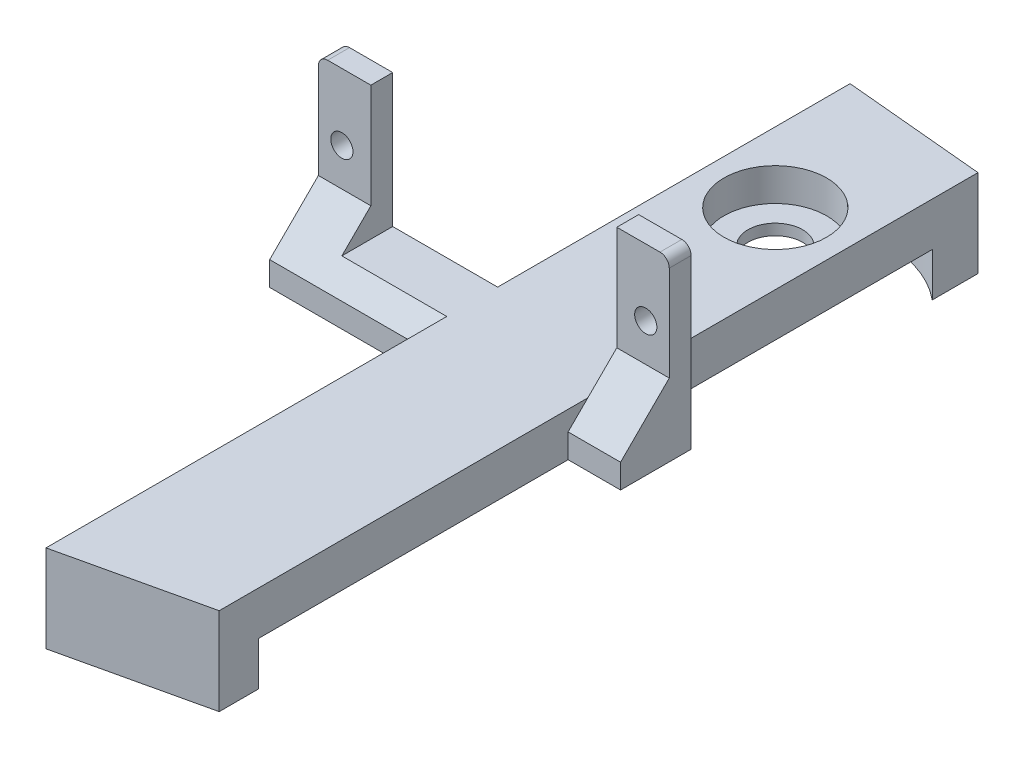
SolidWorks part; units mm, degrees
note: The reader was unsure of these and kept them because the rebuilt part matched: shared geometry of "Sketch2<3>".
ref_plane "Front Plane" through (0, 0, 0) normal (0, 0, 1) x (1, 0, 0)
ref_plane "Top Plane" through (0, 0, 0) normal (0, 1, 0) x (1, 0, 0)
ref_plane "Right Plane" through (0, 0, 0) normal (1, 0, 0) x (0, 0, -1)
sketch "Sketch1" plane through (0, 0, 0) normal (0, 0, 1) x (1, 0, 0)
  line L0 (11.25, -6.1) -> (15.2, -6.1)
  line L1 (11.25, -6.1) -> (11.25, 6.0941)
  line L2 (11.25, 6.0941) -> (15.2, 6.1)
  line L3 (15.2, -6.1) -> (-15.2, -6.1) construction
  line L4 (-10.5, 6.1) -> (-15.2, 6.1) construction
  line L5 (-16.05, 5.25) -> (-16.05, -5.25) construction
  line L6 (-16.05, -5.25) -> (-16.05, -0.55) construction
  line L9 (15.2, -6.1) -> (11.25, -6.1)
  line L10 (-11.25, 6.1) -> (-15.2, 6.1)
  line L11 (-16.05, 5.25) -> (-16.05, -5.25)
  line L12 (-16.05, -5.25) -> (-16.05, -0.55)
  line L13 (16.05, 5.25) -> (16.05, -5.25)
  line L14 (-15.2, -6.1) -> (-16.05, -6.1)
  line L15 (-11.25, 6.1) -> (-11.25, -6.1)
  line L16 (-11.25, -5.25) -> (-11.25, 5.25) construction
  line L17 (-11.25, -5.25) -> (-11.25, 5.25) construction
  line L18 (-15.2, 6.1) -> (15.2, 6.1) construction
  line L19 (-11.25, -6.1) -> (-15.2, -6.1)
  line L20 (-16.05, -5.25) -> (-16.05, -6.1)
  line L21 (15.2, -6.1) -> (16.05, -6.1)
  line L22 (16.05, -5.25) -> (16.05, -6.1)
  arc A0 (-15.2, 6.1) -> (-16.05, 5.25) centre (-15.2, 5.25) ccw construction
  arc A1 (-16.05, -5.25) -> (-15.2, -6.1) centre (-15.2, -5.25) ccw construction
  arc A2 (15.2, -6.1) -> (16.05, -5.25) centre (15.2, -5.25) ccw construction
  arc A3 (16.05, 5.25) -> (15.2, 6.1) centre (15.2, 5.25) ccw construction
  arc A4 (-15.2, 6.1) -> (-16.05, 5.25) centre (-15.2, 5.25) ccw
  arc A5 (-16.05, -5.25) -> (-15.2, -6.1) centre (-15.2, -5.25) ccw
  arc A6 (15.2, -6.1) -> (16.05, -5.25) centre (15.2, -5.25) ccw
  arc A7 (16.05, 5.25) -> (15.2, 6.1) centre (15.2, 5.25) ccw
  circle A8 centre (-13.9, 0) radius 1.016
  circle A9 centre (13.9, 0) radius 1.016
  dimension "D1" = 2.032
  dimension "D2" = 2.032
extrude "Boss-Extrude1" add sketch "Sketch1" along normal blind 2 contours L11 A5 L19 L15 L10 A4 A8 | L13 A7 L2 L1 L0 A6 A9 | A6 L21 L22 | A5 L20 L14
sketch "Sketch2" plane through (0, -6.1, 0) normal (0, -1, 0) x (1, 0, 0)
  line L0 (-16.05, 2) -> (16.05, 2)
  line L5 (16.05, 2) -> (16.05, 0)
  line L6 (16.05, 0) -> (-16.05, 0)
  line L7 (-16.05, 0) -> (-16.05, 2)
  line L8 (-1.65, 41.3173) -> (-1.65, -32.2403)
  line L9 (11.25, 2) -> (11.25, 38.373)
  line L10 (-1.65, -32.2403) -> (11.25, -31.0433)
  line L12 (-27.6754, 45.6063) -> (7.1754, 36.8937) construction
  line L17 (4.75, -29) -> (0.35, -29) construction
  line L18 (-1.65, 39.1) -> (7.1754, 36.8937)
  line L19 (11.25, 0) -> (11.25, -31.0433)
  line L24 (4.75, -29) -> (0.35, -29)
  line L26 (4.75, -29.2) -> (0.35, -29.2)
  line L27 (-1.65, 38.8938) -> (7.1268, 36.6996)
  line L28 (11.12, 34.6396) -> (11.25, 34.5185)
  line L29 (-1.5749, 22.2572) -> (-1.65, 22.613)
  line L30 (-1.65, 41.3173) -> (11.25, 38.373)
  line L32 (-1.6985, 38.906) -> (7.1268, 36.6996) construction
  circle A1 centre (4.75, -19) radius 4.7
  arc A2 (14.75, 27.1922) -> (7.1754, 36.8937) centre (4.75, 27.1922) ccw construction
  arc A3 (4.75, -29) -> (14.75, -19) centre (4.75, -19) ccw construction
  arc A4 (-9.725, -26.277) -> (0.35, -29) centre (0.35, -9) ccw construction
  arc A5 (11.25, 34.7916) -> (7.1754, 36.8937) centre (4.75, 27.1922) ccw
  arc A10 (4.75, -29) -> (11.25, -26.5993) centre (4.75, -19) ccw
  arc A12 (-1.65, -28.8997) -> (0.35, -29) centre (0.35, -9) ccw
  arc A13 (-1.65, -29.1007) -> (0.35, -29.2) centre (0.35, -9) ccw
  arc A14 (4.75, -29.2) -> (11.25, -26.8607) centre (4.75, -19) ccw
  arc A15 (11.12, 34.6396) -> (7.1268, 36.6996) centre (4.75, 27.1922) ccw
  arc A17 (4.75, -29.2) -> (11.38, -26.7513) centre (4.75, -19) ccw construction
  arc A18 (-1.67, -29.0987) -> (0.35, -29.2) centre (0.35, -9) ccw construction
  point P3 (4.75, -19)
  point P28 (-6.5991, -18.7771)
  point P29 (-19.7755, -35.4742)
  point P30 (3.3836, -37.5589)
  point P31 (14.7015, -26.7317)
  point P32 (3.6798, -24.3792)
  point P33 (-7.2167, -27.2566)
  point P37 (4.75, -19)
  point P38 (4.75, -29.2)
  point P39 (12.8214, 0)
  point P40 (11.38, -26.7513)
  point P43 (12.8214, 6.5789)
  point P44 (-80.0361, -11.1071)
  point P45 (-172.8435, 6.8395)
  point P46 (-2.7186, 49.3707)
  point P47 (-2.7186, 0)
  point P50 (8.5784, 18.1443)
  point P51 (5.1008, 9.2671)
  point P52 (11.3818, 16.4399)
  dimension "D3" = 6.4
  dimension "D6" = 9.4
  dimension "D4" = 6.5
  dimension "D5" = 0.2
extrude "Boss-Extrude2" add sketch "Sketch2" along normal blind 3
extrude "Boss-Extrude5" add sketch "Sketch2<3>" along normal blind 8 contours A5 L9 L30 L8 L18 | A14 L26 A13 L8 L10 L19
sketch "Sketch2<3>" plane through (0, -6.1, 0) normal (0, -1, 0) x (1, 0, 0) same geometry as "Sketch2"
sketch "Sketch3" plane through (11.25, 0, 0) normal (1, 0, 0) x (0, 0, -1)
  line L0 (-7.6658, -9.1) -> (-2, -3.4575)
  line L1 (-2, -9.1) -> (-34.7916, -9.1) construction
  line L2 (-2, -9.1) -> (-2, 5.25) construction
  line L3 (-2, -3.4575) -> (-2, -9.1)
  line L4 (-2, -9.1) -> (-7.6658, -9.1)
  line L5 (-2, -6.1) -> (-2, 6.0941) construction
extrude "Boss-Extrude6" add sketch "Sketch3" along normal up to surface and the other way up to surface up to face at (16.05, -1.925, 1) other way up to face at (-16.05, -1.925, 1)
sketch "Sketch4" plane through (0, -6.1, 0) normal (0, 1, 0) x (1, 0, 0)
  line L0 (-11.25, 0) -> (-11.25, -14.1277)
  line L1 (-11.25, -14.1277) -> (11.25, -14.1277)
  line L2 (11.25, -4.6534) -> (11.25, -38.373) construction
  line L3 (11.25, -14.1277) -> (11.25, 0)
  line L4 (11.25, 0) -> (-11.25, 0)
extrude "Cut-Extrude1" cut sketch "Sketch4" along normal blind 7
fillet "Fillet1" radius 0.5 2 edges at (-8.85, -9.1, 7.6658) (13.65, -9.1, 7.6658)
sketch "Sketch5" plane through (0, -9.1, 0) normal (0, -1, 0) x (1, 0, 0)
  line L3 (-1.65, 39.1) -> (-1.65, 6.4552)
  line L14 (0.35, -29.2) -> (4.75, -29.2)
  line L15 (-1.65, 39.1) -> (-1.65, 6.4552)
  line L16 (-16.05, 0) -> (-1.65, 0)
  line L17 (-1.65, 6.4552) -> (-16.05, 6.4552)
  line L18 (-1.65, 6.4552) -> (-16.05, 6.4552)
  line L19 (-16.05, 6.4552) -> (-16.05, 0)
  line L20 (-16.05, 6.4552) -> (-16.05, 0)
  line L21 (16.05, 0) -> (16.05, 6.4552)
  line L22 (-1.65, 0) -> (-1.65, -29.1007)
  line L23 (-1.65, 0) -> (-1.65, -29.1007)
  line L24 (0.35, -29.2) -> (4.75, -29.2)
  line L29 (-16.05, 0) -> (-1.65, 0)
  line L34 (16.05, 0) -> (16.05, 6.4552)
  line L39 (11.25, -26.8607) -> (11.25, 0)
  line L40 (11.25, -26.8607) -> (11.25, 0)
  line L41 (11.25, 0) -> (16.05, 0)
  line L42 (11.25, 0) -> (16.05, 0)
  line L43 (16.05, 6.4552) -> (11.25, 6.4552)
  line L44 (16.05, 6.4552) -> (11.25, 6.4552)
  line L45 (11.25, 6.4552) -> (11.25, 34.7916)
  line L46 (11.25, 6.4552) -> (11.25, 34.7916)
  line L52 (7.1754, 36.8937) -> (-1.65, 39.1)
  line L57 (7.1754, 36.8937) -> (-1.65, 39.1)
  circle A0 centre (4.75, -19) radius 2.5
  arc A2 (-1.65, -29.1007) -> (0.35, -29.2) centre (0.35, -9) ccw
  arc A5 (-1.65, -29.1007) -> (0.35, -29.2) centre (0.35, -9) ccw
  arc A15 (4.75, -29.2) -> (11.25, -26.8607) centre (4.75, -19) ccw
  arc A18 (4.75, -29.2) -> (11.25, -26.8607) centre (4.75, -19) ccw
  arc A21 (11.25, 34.7916) -> (7.1754, 36.8937) centre (4.75, 27.1922) ccw
  arc A22 (11.25, 34.7916) -> (7.1754, 36.8937) centre (4.75, 27.1922) ccw
  dimension "D1" = 5
  dimension "D2" = 0
extrude "Boss-Extrude7" add sketch "Sketch5" along normal blind 1
sketch "Sketch6" plane through (0, 0, 6.4552) normal (0, 0, 1) x (1, 0, 0)
  line L1 (11.25, -10.1) -> (16.5637, -10.1)
  line L2 (11.25, -10.1) -> (11.25, -5.5007)
  line L3 (11.25, -5.5007) -> (16.5637, -5.5007)
  line L4 (16.5637, -10.1) -> (16.5637, -5.5007)
  line L5 (-1.65, -10.1) -> (-17.8132, -10.1)
  line L6 (-1.65, -10.1) -> (-1.65, -4.7554)
  line L7 (-1.65, -4.7554) -> (-17.8132, -4.7554)
  line L8 (-17.8132, -10.1) -> (-17.8132, -4.7554)
extrude "Cut-Extrude2" cut sketch "Sketch6" along normal blind 5
